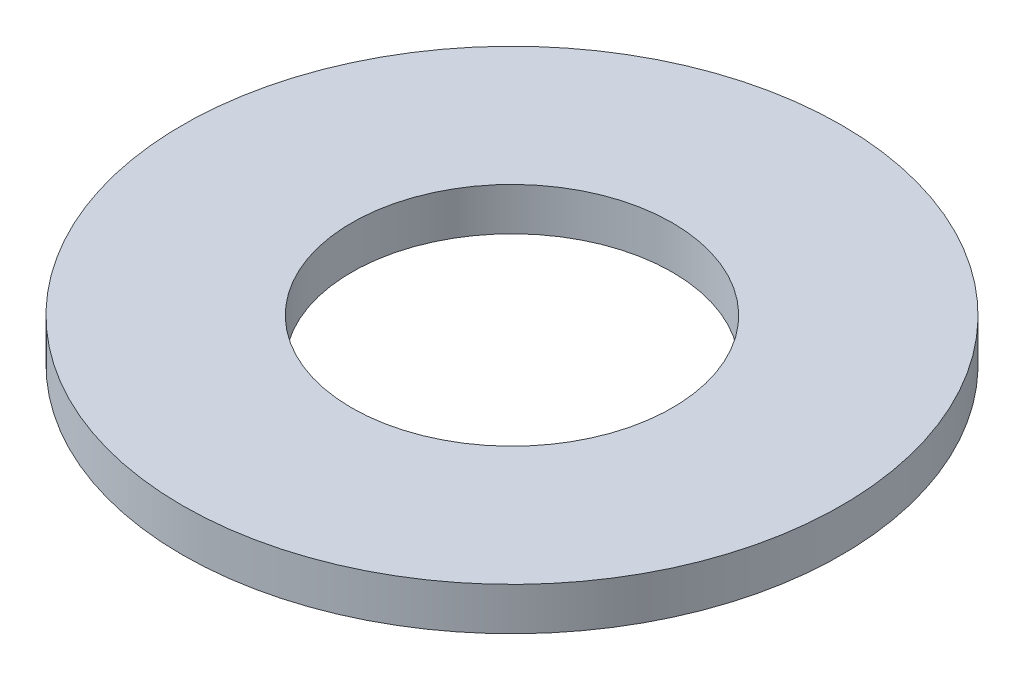
SolidWorks part; units mm, degrees
ref_plane "Front Plane" through (0, 0, 0) normal (0, 0, 1) x (1, 0, 0)
ref_plane "Top Plane" through (0, 0, 0) normal (0, 1, 0) x (1, 0, 0)
ref_plane "Right Plane" through (0, 0, 0) normal (1, 0, 0) x (0, 0, -1)
sketch "Sketch1" plane through (0, 0, 0) normal (0, 1, 0) x (1, 0, 0)
  circle A0 centre (0, 0) radius 9.25
  circle A1 centre (0, 0) radius 4.5
  dimension "D1" = 18.5
  dimension "D2" = 9
extrude "Boss-Extrude1" add sketch "Sketch1" against normal blind 1.2
